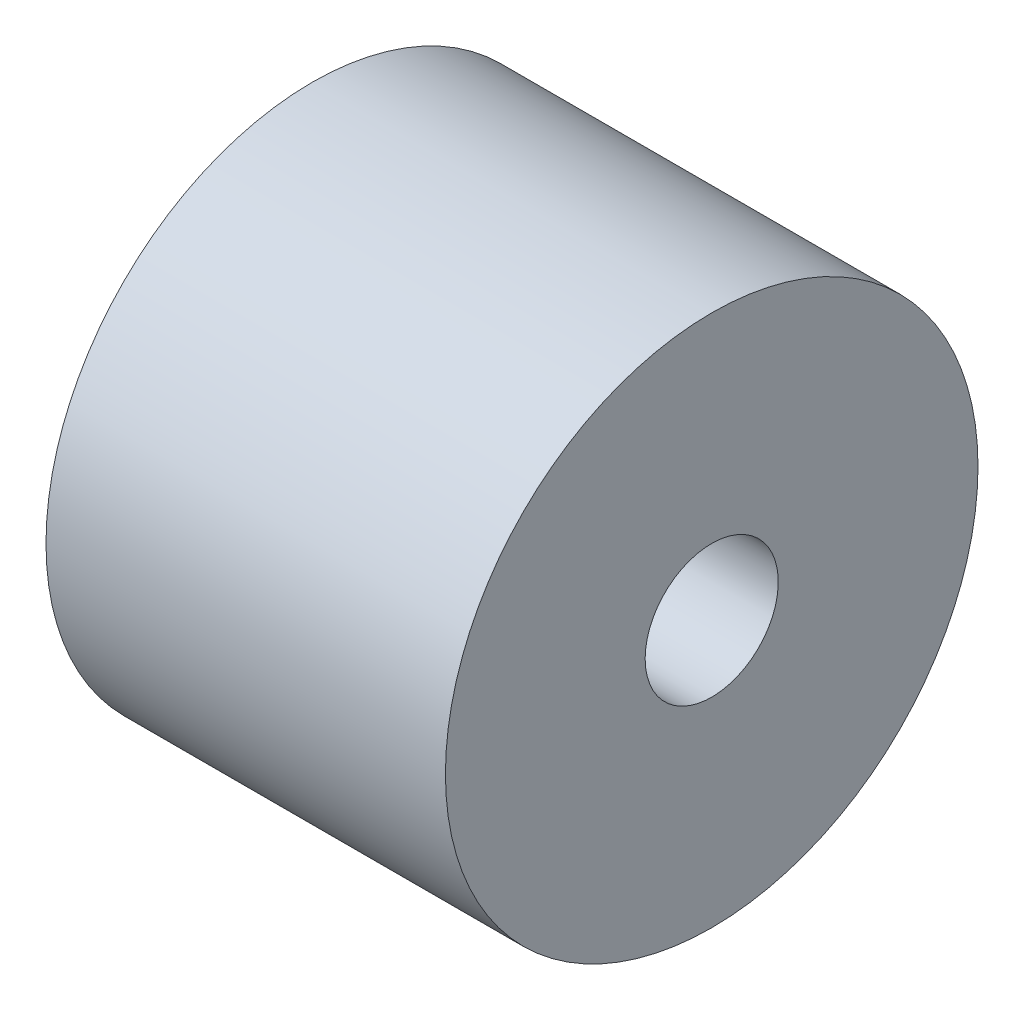
SolidWorks part; units mm, degrees
ref_plane "Front Plane" through (0, 0, 0) normal (0, 0, 1) x (1, 0, 0)
ref_plane "Top Plane" through (0, 0, 0) normal (0, 1, 0) x (1, 0, 0)
ref_plane "Right Plane" through (0, 0, 0) normal (1, 0, 0) x (0, 0, -1)
sketch "Grommet_IMU Sketch" plane through (0, 0, 0) normal (0, 0, 1) x (1, 0, 0)
  line L0 (-400, 0) -> (400, 0) construction
  line L1 (0, 1) -> (6, 1)
  line L2 (6, 1) -> (6, 4)
  line L3 (6, 4) -> (0, 4)
  line L4 (0, 4) -> (0, 1)
revolve "Grommet_IMU" add sketch "Grommet_IMU Sketch" angle 360 about L0
ref_axis "Engine Axis" through (6.3, 0, 0) along (-1, 0, 0)
